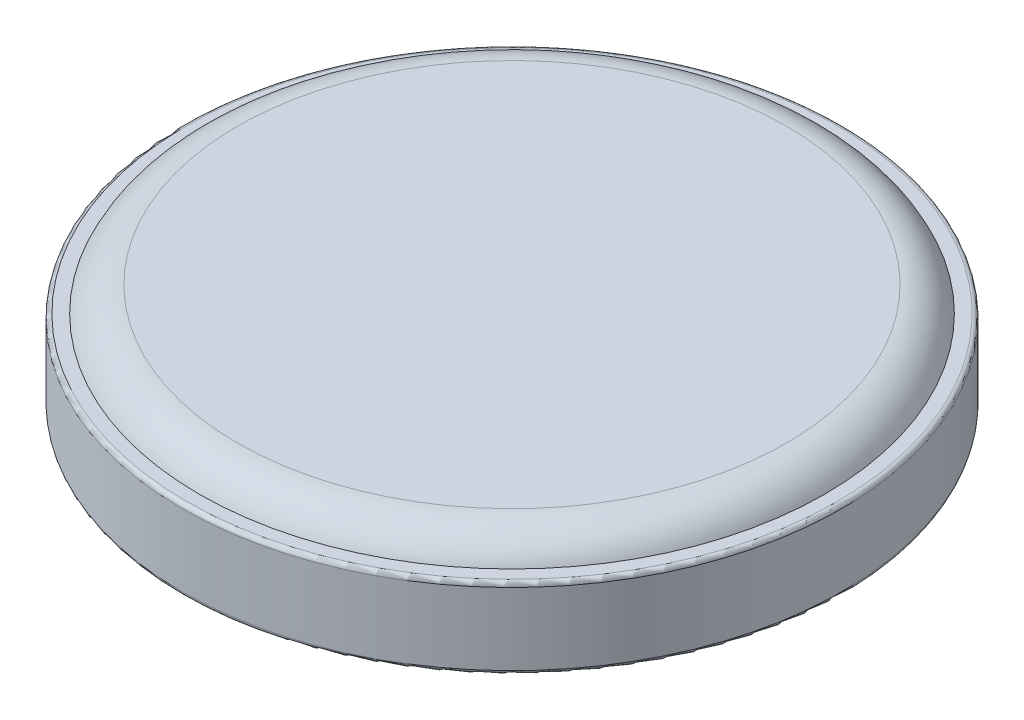
SolidWorks part; units mm, degrees
ref_plane "Front Plane" through (0, 0, 0) normal (0, 0, 1) x (1, 0, 0)
ref_plane "Top Plane" through (0, 0, 0) normal (0, 1, 0) x (1, 0, 0)
ref_plane "Right Plane" through (0, 0, 0) normal (1, 0, 0) x (0, 0, -1)
sketch "Sketch1" plane through (0, 0, 0) normal (0, 1, 0) x (1, 0, 0)
  circle A0 centre (0, 0) radius 10
  dimension "D1" = 20
extrude "Boss-Extrude1" add sketch "Sketch1" along normal blind 3.2
sketch "Sketch2" plane through (0, 3.2, 0) normal (0, 1, 0) x (1, 0, 0)
  circle A0 centre (0, 0) radius 10
  circle A1 centre (0, 0) radius 9.492
  circle A2 centre (0, 0) radius 10 construction
  dimension "D1" = 0.508
  dimension "D2" = 0
extrude "Cut-Extrude1" cut sketch "Sketch2" against normal blind 0.762
fillet "Fillet3" radius 1.27 1 edges at (0, 3.2, 9.492)
fillet "Fillet2" radius 0.127 2 edges at (0, 0, 10) (0, 2.438, 10)
